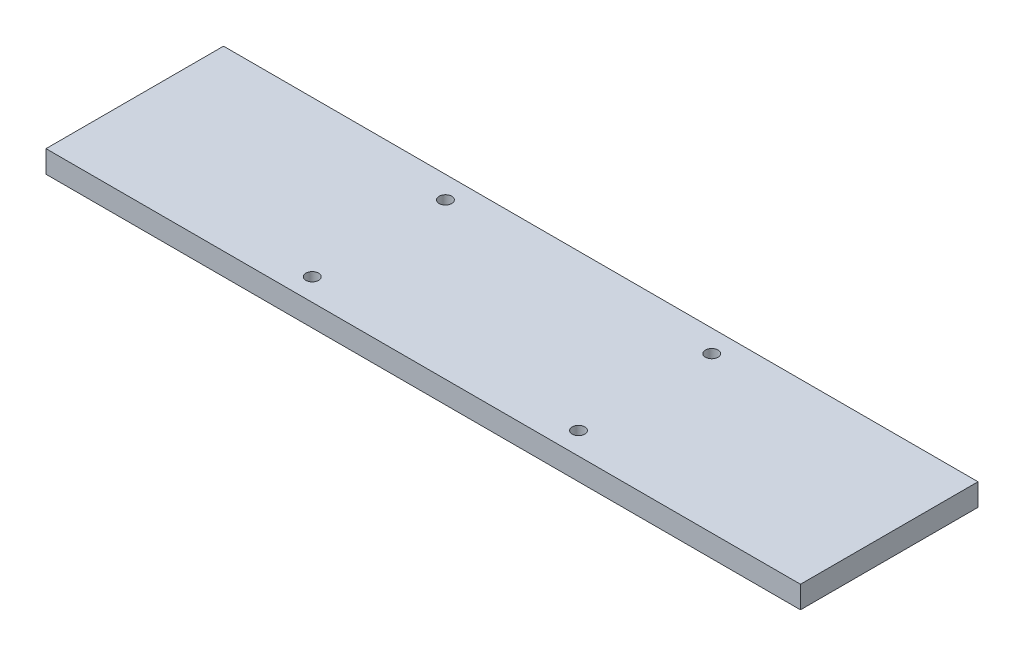
SolidWorks part; units mm, degrees
ref_plane "Front Plane" through (0, 0, 0) normal (0, 0, 1) x (1, 0, 0)
ref_plane "Top Plane" through (0, 0, 0) normal (0, 1, 0) x (1, 0, 0)
ref_plane "Right Plane" through (0, 0, 0) normal (1, 0, 0) x (0, 0, -1)
sketch "Sketch1" plane through (0, 0, 0) normal (0, 1, 0) x (1, 0, 0)
  line L1 (-107.95, -25.4) -> (107.95, -25.4)
  line L2 (-107.95, -25.4) -> (-107.95, 25.4)
  line L3 (-107.95, 25.4) -> (107.95, 25.4)
  line L4 (107.95, -25.4) -> (107.95, 25.4)
  line L5 (-107.95, -25.4) -> (107.95, 25.4) construction
  line L6 (-107.95, 25.4) -> (107.95, -25.4) construction
  line L7 (38.1, -19.05) -> (-38.1, -19.05) construction
  line L8 (38.1, -19.05) -> (38.1, 19.05) construction
  line L9 (38.1, 19.05) -> (-38.1, 19.05) construction
  line L10 (-38.1, -19.05) -> (-38.1, 19.05) construction
  line L11 (38.1, -19.05) -> (-38.1, 19.05) construction
  line L12 (38.1, 19.05) -> (-38.1, -19.05) construction
  circle A0 centre (-38.1, 19.05) radius 1.8097
  circle A1 centre (-38.1, -19.05) radius 1.8097
  circle A2 centre (38.1, 19.05) radius 1.8097
  circle A3 centre (38.1, -19.05) radius 1.8097
  point P0 (0, 0)
  point P14 (0, 0)
  point P15 (0, 0)
  point P19 (0, 0)
  point P20 (0, 0)
  dimension "D3" = 3.6195
  dimension "D4" = 38.1
  dimension "D1" = 215.9
  dimension "D2" = 50.8
  dimension "D5" = 76.2
extrude "Boss-Extrude1" add sketch "Sketch1" along normal blind 6.35
